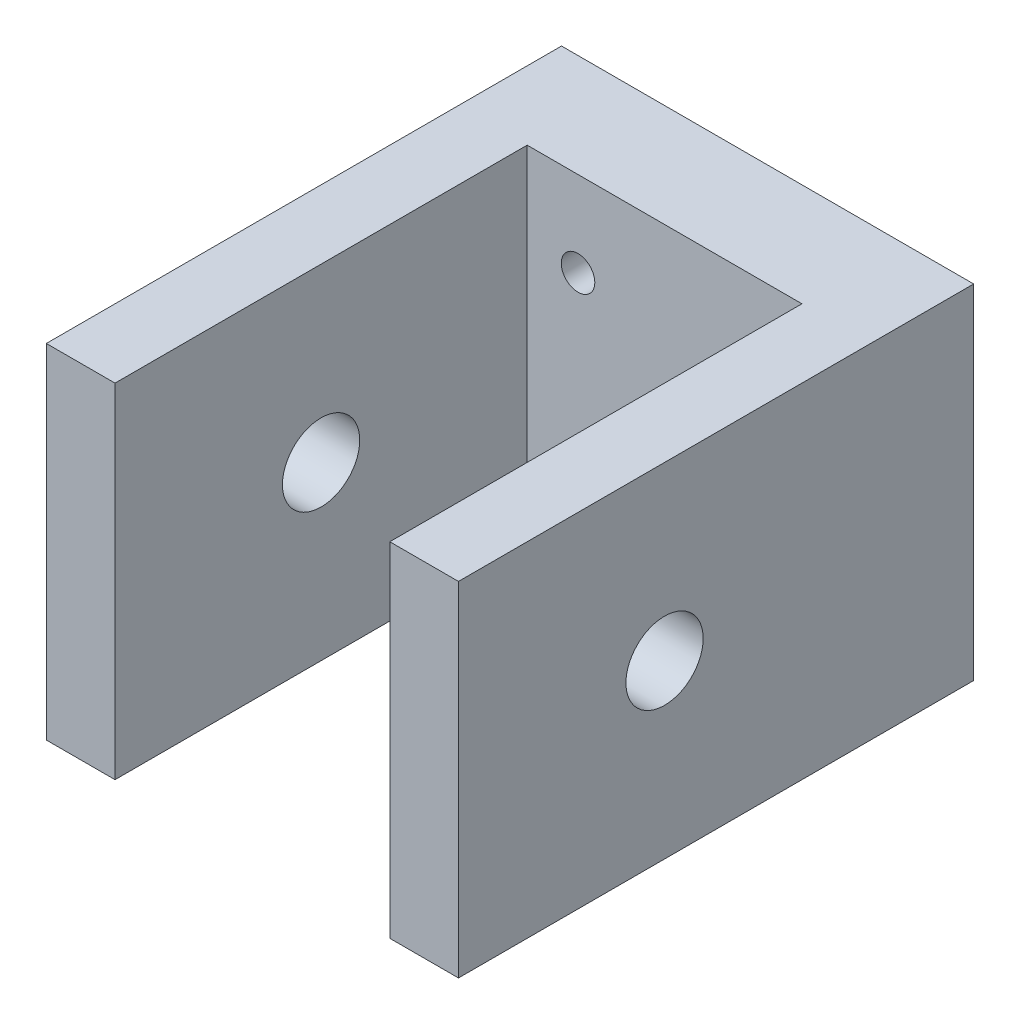
SolidWorks part; units mm, degrees
ref_plane "Front Plane" through (0, 0, 0) normal (0, 0, 1) x (1, 0, 0)
ref_plane "Top Plane" through (0, 0, 0) normal (0, 1, 0) x (1, 0, 0)
ref_plane "Right Plane" through (0, 0, 0) normal (1, 0, 0) x (0, 0, -1)
sketch "Sketch2" plane through (0, 0, 0) normal (0, 1, 0) x (1, 0, 0)
  line L0 (-12.7, 0) -> (-12.7, -38.1)
  line L1 (-12.7, -38.1) -> (-19.05, -38.1)
  line L2 (-19.05, -38.1) -> (-19.05, 9.525)
  line L3 (-19.05, 9.525) -> (19.05, 9.525)
  line L4 (19.05, 9.525) -> (19.05, -38.1)
  line L5 (19.05, -38.1) -> (12.7, -38.1)
  line L6 (12.7, -38.1) -> (12.7, 0)
  line L7 (12.7, 0) -> (-12.7, 0)
  point P9 (0, 0)
  dimension "D1" = 25.4
  dimension "D2" = 6.35
  dimension "D3" = 9.525
  dimension "D4" = 38.1
extrude "Boss-Extrude1" add sketch "Sketch2" along normal mid plane 31.75
hole_wizard "M2.5 Clearance Hole1" positions "Sketch3" profile "Sketch4" hole size "M2.5" standard "ANSI Metric" end condition through all
sketch "Sketch3" plane through (0, 0, -9.525) normal (0, 0, -1) x (-1, 0, 0)
  line L1 (8, -8) -> (-8, -8)
  line L2 (8, -8) -> (8, 8)
  line L3 (8, 8) -> (-8, 8)
  line L4 (-8, -8) -> (-8, 8)
  line L5 (8, -8) -> (-8, 8) construction
  line L6 (8, 8) -> (-8, -8) construction
  point P0 (8, 8)
  point P2 (-8, 8)
  point P4 (-8, -8)
  point P6 (8, -8)
  point P60 (0, 0)
  dimension "D1" = 16
sketch "Sketch4" plane through (-8, 8, -9.525) normal (1, 0, 0) x (0, 1, 0)
  line L0 (0, 0) -> (0, 47.625)
  line L1 (0, 47.625) -> (1.55, 47.625)
  line L2 (1.55, 47.625) -> (1.55, 0)
  line L5 (1.55, 0) -> (0, 0)
  line L11 (0, -6.35) -> (0, 107.95) construction
  dimension "Thru Hole Dia." = 3.1
  dimension "Thru Hole Depth" = 47.625
hole_wizard "1/4 Clearance Hole1" positions "Sketch5" profile "Sketch6" hole size "1/4" standard "ANSI Inch" end condition through all
sketch "Sketch5" plane through (19.05, 0, 0) normal (1, 0, 0) x (0, 0, -1)
  line L0 (0, -15.875) -> (-38.1, -15.875) construction
  point P0 (-19.05, 0)
  point P5 (-19.05, -15.875)
sketch "Sketch6" plane through (19.05, 0, 19.05) normal (0, 1, 0) x (0, 0, -1)
  line L0 (0, 0) -> (0, 38.1)
  line L1 (0, 38.1) -> (3.5712, 38.1)
  line L2 (3.5712, 38.1) -> (3.5712, 0)
  line L5 (3.5712, 0) -> (0, 0)
  line L11 (0, -6.35) -> (0, 107.95) construction
  dimension "Thru Hole Dia." = 7.1425
  dimension "Thru Hole Depth" = 38.1
ref_plane "Plane1" through (0, 0, -4.7625) normal (0, 0, 1) x (1, 0, 0)
sketch "Sketch7" plane through (0, 0, -4.7625) normal (0, 0, 1) x (1, 0, 0)
  line L1 (11.0734, 10.7241) -> (4.9266, 10.7241)
  line L2 (11.0734, 10.7241) -> (11.0734, 5.2758)
  line L3 (11.0734, 5.2758) -> (4.9266, 5.2758)
  line L4 (4.9266, 10.7241) -> (4.9266, 5.2758)
  line L5 (11.0734, 10.7241) -> (4.9266, 5.2758) construction
  line L6 (11.0734, 5.2758) -> (4.9266, 10.7241) construction
  line L7 (-4.9266, 10.7241) -> (-11.0734, 10.7241)
  line L8 (-4.9266, 10.7241) -> (-4.9266, 5.2758)
  line L9 (-4.9266, 5.2758) -> (-11.0734, 5.2758)
  line L10 (-11.0734, 10.7241) -> (-11.0734, 5.2758)
  line L11 (-4.9266, 10.7241) -> (-11.0734, 5.2758) construction
  line L12 (-4.9266, 5.2758) -> (-11.0734, 10.7241) construction
  line L13 (-4.9266, -5.2759) -> (-11.0734, -5.2759)
  line L14 (-4.9266, -5.2759) -> (-4.9266, -10.7242)
  line L15 (-4.9266, -10.7242) -> (-11.0734, -10.7242)
  line L16 (-11.0734, -5.2759) -> (-11.0734, -10.7242)
  line L17 (-4.9266, -5.2759) -> (-11.0734, -10.7242) construction
  line L18 (-4.9266, -10.7242) -> (-11.0734, -5.2759) construction
  line L19 (11.0734, -5.2759) -> (4.9266, -5.2759)
  line L20 (11.0734, -5.2759) -> (11.0734, -10.7242)
  line L21 (11.0734, -10.7242) -> (4.9266, -10.7242)
  line L22 (4.9266, -5.2759) -> (4.9266, -10.7242)
  line L23 (11.0734, -5.2759) -> (4.9266, -10.7242) construction
  line L24 (11.0734, -10.7242) -> (4.9266, -5.2759) construction
  point P0 (8, 8)
  point P6 (-8, 8)
  point P12 (-8, -8)
  point P18 (8, -8)
  dimension "D1" = 6.1468
  dimension "D2" = 5.4483
extrude "Cut-Extrude1" cut sketch "Sketch7" against normal mid plane 2.3542
